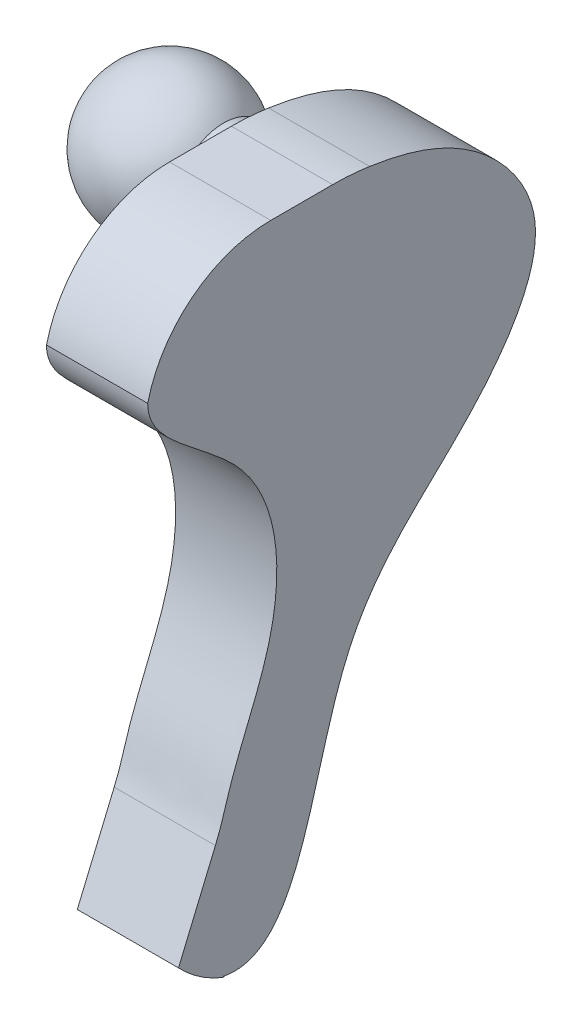
SolidWorks part; units mm, degrees
ref_plane "Front Plane" through (0, 0, 0) normal (0, 0, 1) x (1, 0, 0)
ref_plane "Top Plane" through (0, 0, 0) normal (0, 1, 0) x (1, 0, 0)
ref_plane "Right Plane" through (0, 0, 0) normal (1, 0, 0) x (0, 0, -1)
sketch "Sketch1" plane through (0, 0, 0) normal (1, 0, 0) x (0, 0, -1)
  line L1 (6.4425, 0) -> (13.4096, 0)
  line L2 (1.4425, -5) -> (1.4425, -20.3454)
  line L3 (6.4425, -25.3454) -> (13.4096, -25.3454)
  line L4 (18.4096, -5) -> (18.4096, -20.3454)
  arc A0 (18.4096, -20.3454) -> (13.4096, -25.3454) centre (13.4096, -20.3454) cw
  arc A1 (1.4425, -5) -> (6.4425, 0) centre (6.4425, -5) cw
  arc A2 (6.4425, -25.3454) -> (1.4425, -20.3454) centre (6.4425, -20.3454) cw
  arc A3 (13.4096, 0) -> (18.4096, -5) centre (13.4096, -5) cw
  dimension "D1" = 5
extrude "Boss-Extrude1" add sketch "Sketch1" along normal blind 4
sketch "Sketch2" plane through (4, 0, 0) normal (1, 0, 0) x (0, 0, -1)
  spline S0 degree 3 poles (6.1636, 0.1508) (10.199, 0.0572) (14.4094, -0.8858) (18.0931, -5.601) (14.0349, -11.5069) (8.1911, -15.2394) (7.5753, -27.2833) (1.4433, -23.3045) (4.1815, -21.148) (4.8745, -17.9621) (7.119, -13.8027) (6.544, -7.5303) (0.4242, -4.848) (3.0332, -0.8121) (6.1636, 0.1508) (10.199, 0.0572) (14.4094, -0.8858) knots -0.142893 -0.102323 -0.045145 0 0.077946 0.143334 0.228663 0.345497 0.493272 0.53045 0.570401 0.608237 0.680812 0.77859 0.857107 0.897677 0.954855 1 1.077946 1.143334 1.228663 only from (9.464, 0) to (9.464, 0)
  spline S1 degree 3 poles (4.4068, -24.866) (5.6433, -25.5656) (9.3275, -24.3965) (20.9491, -37.6374) (40.108, 7.0467) (11.0672, 5.0457) (-13.2243, 4.1043) (-4.6942, -20.162) (2.4698, -23.3042) knots 0 0 0 0 0.03846 0.097297 0.409886 0.59367 0.74447 1 1 1 1
  arc M1 (13.4096, -25.3454) -> (18.4096, -20.3454) centre (13.4096, -20.3454) ccw
  line M2 (18.4096, -20.3454) -> (18.4096, -5)
  arc M3 (18.4096, -5) -> (13.4096, 0) centre (13.4096, -5) ccw
  line M4 (13.4096, 0) -> (6.4425, 0)
  arc M5 (6.4425, 0) -> (1.4425, -5) centre (6.4425, -5) ccw
  line M6 (1.4425, -5) -> (1.4425, -20.3454)
  arc M7 (1.4425, -20.3454) -> (6.4425, -25.3454) centre (6.4425, -20.3454) ccw
  line M8 (6.4425, -25.3454) -> (13.4096, -25.3454)
extrude "Cut-Extrude3" cut sketch "Sketch2" against normal blind 10 contours S1 S0 M7 M5 M6 | S0 S1 M8 M1 M2 M3 M4 | S1 S0 M8 M7 M6 M5 M4 M3 M2 M1 region at (4, 0.0873, -4.3353) region at (4, -16.5391, -13.9483) region at (4, -13.5158, -3.5381)
sketch "Sketch6" plane through (4, 0, 0) normal (1, 0, 0) x (0, 0, -1)
  spline S0 degree 3 poles (10.1982, -25.4378) (6.9194, -24.2688) (5.7052, -25.181) (2.9672, -24.644) (6.7987, -26.5247) (10.1982, -25.4378) (6.9194, -24.2688) (5.7052, -25.181) knots -0.737157 -0.423816 -0.233145 0 0.142115 0.262843 0.576184 0.766855 1 1.142115 1.262843 1.576184 only from (6.8766, -24.6464) to (6.8766, -24.6464)
extrude "Cut-Extrude4" cut sketch "Sketch6" against normal blind 10
fillet "Fillet4" radius 10 2 edges at (2, 0, -9.464) (2, -3.8336, -1.5805) type face fillet first side face at (2, 0, -7.9533) first side face at (2, -1.4952, -3.6791) second side face at (2, -12.4689, -7.0034) second side face at (2, -13.5598, -2.0047)
sketch "Sketch7" plane through (0, 0, 0) normal (-1, 0, 0) x (0, 0, 1)
  ellipse E0 centre (-12.0792, -5.1769) end of major axis (-11.3485, -3.4945) minor radius 1.6482
extrude "Boss-Extrude2" add sketch "Sketch7" along normal blind 3
sketch "Sketch8" plane through (-3, 0, 0) normal (-1, 0, 0) x (0, 0, 1)
  circle A0 centre (-12.0792, -5.1769) radius 1.9414
extrude "Boss-Extrude3" add sketch "Sketch8" along normal blind 0.5
dome "Dome1" faces to dome 1 distance 5 reverse direction no elliptical dome no face at (-3.5, -5.1769, -10.1378) parameters "D1"=5
sketch "Sketch9" plane through (0, 0, 0) normal (-1, 0, 0) x (0, 0, 1)
  spline S0 degree 1 poles (-4.3258, -20.141) (-2.4862, -24.5054) knots 0 0 1 1
  spline S1 degree 3 poles (-2.4862, -24.5054) (3.7359, -24.1717) (-2.1219, -16.1267) (-4.3258, -20.141) knots 0 0 0 0 1 1 1 1
extrude "Cut-Extrude5" cut sketch "Sketch9" against normal blind 5
